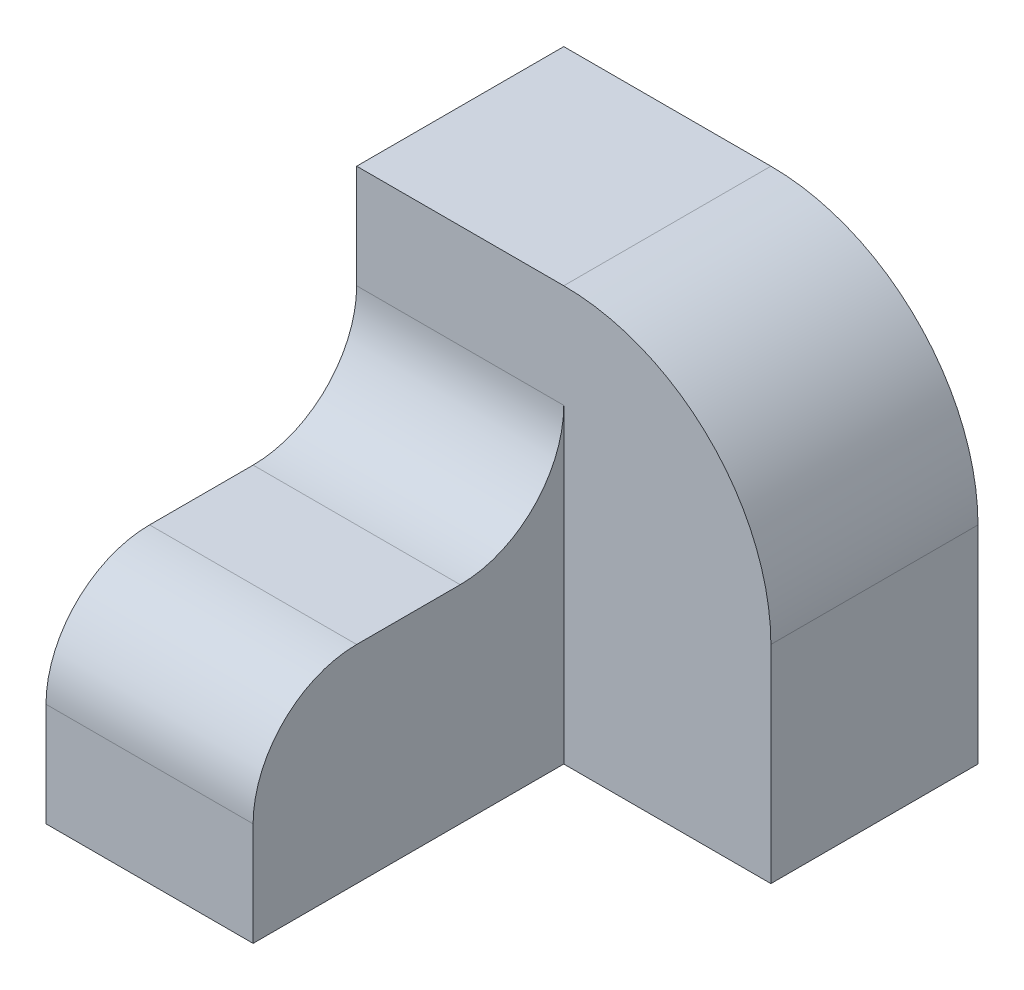
SolidWorks part; units mm, degrees
ref_plane "前基準面" through (0, 0, 0) normal (0, 0, 1) x (1, 0, 0)
ref_plane "上基準面" through (0, 0, 0) normal (0, 1, 0) x (1, 0, 0)
ref_plane "右基準面" through (0, 0, 0) normal (1, 0, 0) x (0, 0, -1)
sketch "草圖1" plane through (0, 0, 0) normal (0, 1, 0) x (1, 0, 0)
  line L1 (0, 0) -> (10, 0)
  line L2 (0, 0) -> (0, -15)
  line L3 (0, -15) -> (10, -15)
  line L4 (10, 0) -> (10, -15)
  line L5 (0, 0) -> (20, 0)
  line L6 (0, 0) -> (0, 10)
  line L7 (0, 10) -> (20, 10)
  line L8 (20, 0) -> (20, 10)
  dimension "D1" = 10
  dimension "D2" = 10
  dimension "D3" = 20
  dimension "D4" = 15
extrude "填料-伸長1" add sketch "草圖1" along normal blind 10 contours L4 L1 L2 L3 region at (5, 0, 7.5)
extrude "填料-伸長2" add sketch "草圖1<3>" along normal blind 20 contours L5 L8 L7 L6 L1 region at (10, 0, -5)
sketch "草圖1<3>" plane through (0, 0, 0) normal (0, 1, 0) x (1, 0, 0) same geometry as "草圖1"
fillet "圓角1" radius 5 2 edges at (5, 10, 0) (5, 10, 15)
fillet "圓角2" radius 10 1 edges at (20, 20, -5)
scale "縮放比例1" scale about centroid uniform scaling yes scale factor 0.2
